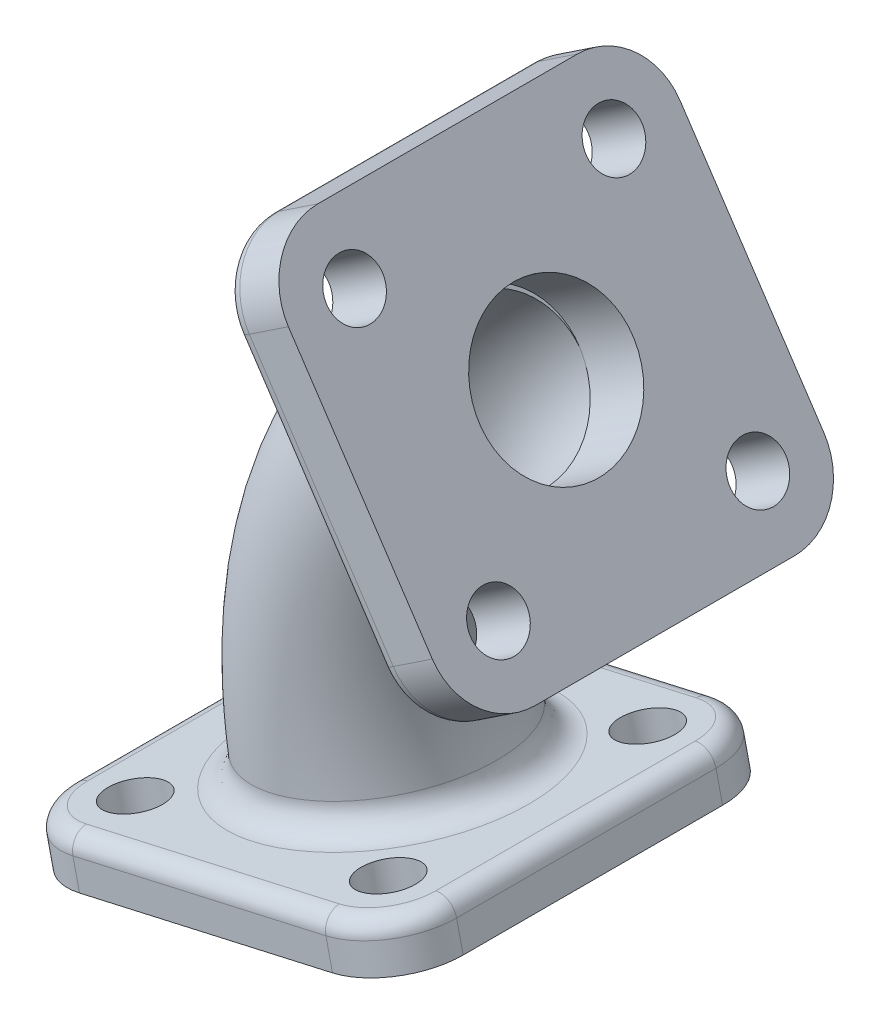
SolidWorks part; units mm, degrees
ref_plane "Front Plane" through (0, 0, 0) normal (0, 0, 1) x (1, 0, 0)
ref_plane "Top Plane" through (0, 0, 0) normal (0, 1, 0) x (1, 0, 0)
ref_plane "Right Plane" through (0, 0, 0) normal (1, 0, 0) x (0, 0, -1)
sketch "Sketch1" plane through (0, 0, 0) normal (0, 0, 1) x (1, 0, 0)
  line L0 (78.8763, 27.5797) -> (-63.4075, 27.5797) construction
  line L1 (78.8763, 27.5797) -> (-289.6374, -340.934) construction
  arc A0 (-63.4075, 27.5797) -> (-158.0409, -209.3376) centre (61.4, -159.6316) ccw
  point P3 (0, 0)
  point P5 (-289.6374, -340.934)
  dimension "D2" = 225
  dimension "D1" = 45
ref_plane "Plane1" through (-63.4075, 27.5797, 0) normal (-0.8321, -0.5547, 0) x (0, 0, 1)
sketch "Sketch2" plane through (-63.4075, 27.5797, 0) normal (-0.8321, -0.5547, 0) x (0, 0, 1)
  line L0 (112.5, 112.5) -> (-112.5, -112.5) construction
  line L1 (-112.5, 112.5) -> (112.5, 112.5)
  line L2 (-112.5, 112.5) -> (-112.5, -112.5)
  line L3 (-112.5, -112.5) -> (112.5, -112.5)
  line L4 (112.5, 112.5) -> (112.5, -112.5)
  dimension "D1" = 225
  dimension "225" = 225
sketch "Sketch5" plane through (-63.4075, 27.5797, 0) normal (-0.8321, -0.5547, 0) x (0, 0, 1)
  circle A0 centre (0, 0) radius 65
  circle A1 centre (0, 0) radius 44
  dimension "D1" = 130
  dimension "D2" = 88
sweep "Sweep1" add profiles "Sketch5" path "Sketch1"
extrude "Boss-Extrude2" add sketch "Sketch2" along normal blind 37
fillet "Fillet1" radius 38 4 edges at (-141.2042, 110.9234, 112.5) (-141.2042, 110.9234, -112.5) (-16.3967, -76.2879, -112.5) (-16.3967, -76.2879, 112.5)
fillet "Fillet2" radius 15 1 edges at (-117.599, 42.1642, 47.1478)
fillet "Fillet3" radius 10 8 edges at (-94.1934, 7.0558, -112.5) (-156.5972, 100.6614, 0) (-94.1934, 7.0558, 112.5) (-31.7896, -86.5499, 0) (-37.9634, -77.2892, 101.3701) (-150.4234, 91.4008, 101.3701) (-150.4234, 91.4008, -101.3701) (-37.9634, -77.2892, -101.3701)
ref_plane "Plane2" through (-125.8113, 121.1854, 74.5) normal (0, 0, 1) x (1, 0, 0)
sketch "Sketch7" plane through (-31.1684, -20.779, 0) normal (0.8321, 0.5547, 0) x (0, 0, -1)
  line L0 (-101.3701, 159.4899) -> (101.3701, -43.2502) construction
  line L1 (-101.3701, -43.2502) -> (101.3701, 159.4899) construction
  line L2 (112.5, 58.1199) -> (-112.5, 58.1199) construction
  line L3 (112.5, 132.6199) -> (112.5, -16.3801) construction
  line L4 (-112.5, -16.3801) -> (-112.5, 132.6199) construction
  circle A3 centre (-74.5, 132.6199) radius 16
  arc A4 (-74.5, 170.6199) -> (-112.5, 132.6199) centre (-74.5, 132.6199) ccw construction
  arc A5 (74.5, -54.3801) -> (112.5, -16.3801) centre (74.5, -16.3801) ccw construction
  arc A6 (-112.5, -16.3801) -> (-74.5, -54.3801) centre (-74.5, -16.3801) ccw construction
  arc A7 (112.5, 132.6199) -> (74.5, 170.6199) centre (74.5, 132.6199) ccw construction
  circle A8 centre (74.5, -16.3801) radius 16
  circle A9 centre (-74.5, -16.3801) radius 16
  circle A10 centre (74.5, 132.6199) radius 16
  circle A11 centre (0, 58.1199) radius 44
  point P5 (-74.5, 132.6199)
  dimension "D1" = 32
  dimension "D2" = 88
extrude "Cut-Extrude1" cut sketch "Sketch7" against normal blind 37
sketch "Sketch8" plane through (37.3903, -165.0701, 0) normal (0.2209, -0.9753, 0) x (0.9753, 0.2209, 0)
  line L0 (-200.3821, 44) -> (-200.3821, -44) construction
  line L2 (-274.8821, 112.5) -> (-125.8821, 112.5)
  line L3 (-312.8821, 74.5) -> (-312.8821, -74.5)
  line L4 (-274.8821, -112.5) -> (-125.8821, -112.5)
  line L5 (-87.8821, 74.5) -> (-87.8821, -74.5)
  line L6 (-312.8821, 112.5) -> (-87.8821, -112.5) construction
  line L7 (-312.8821, -112.5) -> (-87.8821, 112.5) construction
  arc A0 (-312.8821, -74.5) -> (-274.8821, -112.5) centre (-274.8821, -74.5) ccw
  arc A1 (-125.8821, -112.5) -> (-87.8821, -74.5) centre (-125.8821, -74.5) ccw
  arc A2 (-125.8821, 112.5) -> (-87.8821, 74.5) centre (-125.8821, 74.5) cw
  arc A3 (-274.8821, 112.5) -> (-312.8821, 74.5) centre (-274.8821, 74.5) ccw
  circle A4 centre (-274.8821, 74.5) radius 16
  circle A5 centre (-125.8821, 74.5) radius 16
  circle A6 centre (-125.8821, -74.5) radius 16
  circle A7 centre (-274.8821, -74.5) radius 16
  circle A8 centre (-200.3821, 0) radius 44
  point P4 (-200.3821, 0)
  dimension "D3" = 38
  dimension "D4" = 32
  dimension "D5" = 32
  dimension "D6" = 32
  dimension "D7" = 32
  dimension "D1" = 225
  dimension "D2" = 225
extrude "Boss-Extrude3" add sketch "Sketch8" along normal blind 27
fillet "Fillet4" radius 10 8 edges at (-158.0409, -209.3376, 112.5) (-48.3204, -184.4846, 0) (-158.0409, -209.3376, -112.5) (-267.7614, -234.1905, 0) (-59.1754, -186.9434, 101.3701) (-59.1754, -186.9434, -101.3701) (-256.9064, -231.7318, -101.3701) (-256.9064, -231.7318, 101.3701)
fillet "Fillet5" radius 15 1 edges at (-94.6469, -194.9781, 0)
sketch "Sketch9" plane through (43.355, -191.403, 0) normal (0.2209, -0.9753, 0) x (0.9753, 0.2209, 0)
  circle A0 centre (-200.3821, 0) radius 44
  circle A1 centre (-200.3821, 0) radius 65
  dimension "D1" = 88
  dimension "D2" = 130
extrude "Boss-Extrude4" add sketch "Sketch9" along normal blind 7
